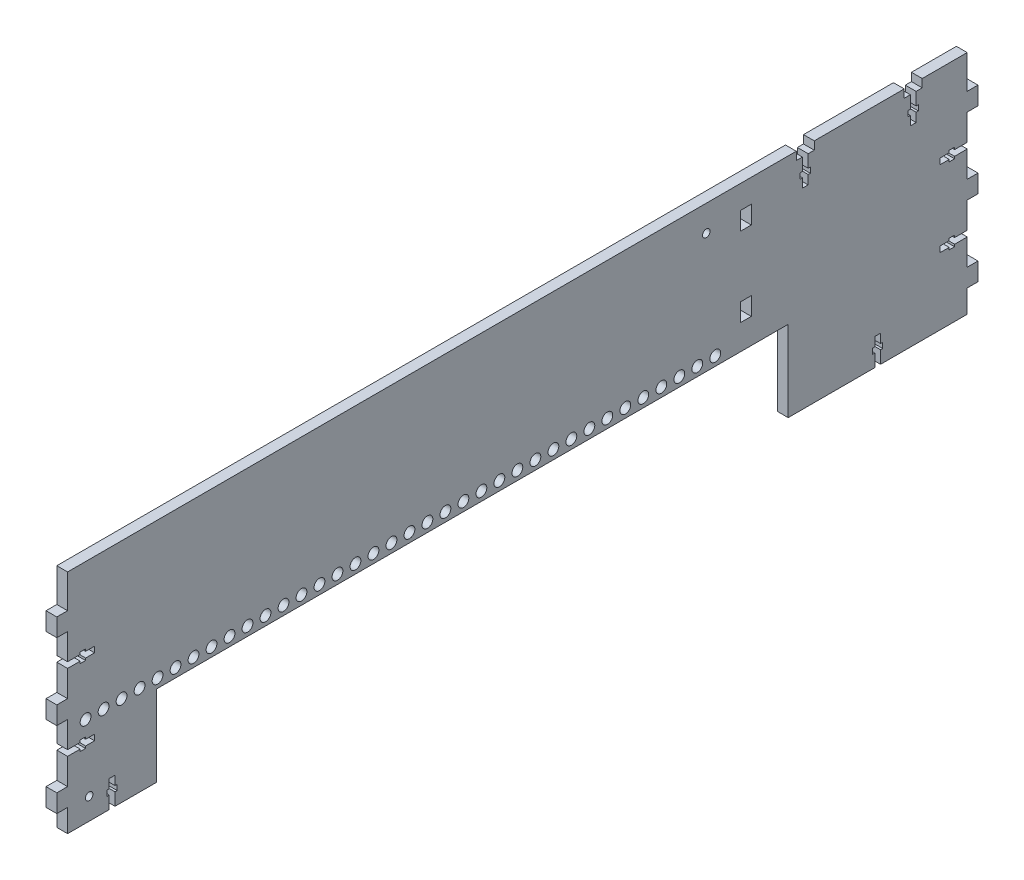
SolidWorks part; units mm, degrees
ref_plane "Front Plane" through (0, 0, 0) normal (0, 0, 1) x (1, 0, 0)
ref_plane "Top Plane" through (0, 0, 0) normal (0, 1, 0) x (1, 0, 0)
ref_plane "Right Plane" through (0, 0, 0) normal (1, 0, 0) x (0, 0, -1)
sketch "Sketch1" plane through (0, 0, 0) normal (1, 0, 0) x (0, 0, -1)
  line L1 (-250, -63) -> (250, -63)
  line L2 (-250, -63) -> (-250, 63)
  line L3 (-250, 63) -> (250, 63)
  line L4 (250, -63) -> (250, 63)
  line L5 (-250, -63) -> (250, 63) construction
  line L6 (-250, 63) -> (250, -63) construction
  point P0 (0, 0)
  dimension "D1" = 126
  dimension "D2" = 500
extrude "Boss-Extrude1" add sketch "Sketch1" along normal blind 6
sketch "Sketch4" plane through (0, 0, 250) normal (0, 0, 1) x (1, 0, 0)
  line L0 (0, 63) -> (0, -63) construction
  line L1 (0, 44.3321) -> (6, 44.3321)
  line L2 (0, 44.3321) -> (0, 34.3321)
  line L3 (0, 34.3321) -> (6, 34.3321)
  line L4 (6, 44.3321) -> (6, 34.3321)
  line L5 (6, 63) -> (6, -63) construction
  line L6 (0, 34.3321) -> (6, 34.3321) construction
  line L7 (0, -69) -> (0, 63) construction
  line L8 (6, 44.3321) -> (0, 44.3321) construction
  line L9 (0, -8) -> (6, -8) construction
  line L10 (0, -8) -> (6, -8)
  line L11 (0, -8) -> (0, 2)
  line L12 (0, 2) -> (6, 2)
  line L13 (6, -8) -> (6, 2)
  line L14 (6, -69) -> (6, 63) construction
  line L15 (6, 2) -> (0, 2) construction
  line L16 (6, -40.3321) -> (0, -40.3321) construction
  line L17 (0, -50.3321) -> (6, -50.3321)
  line L18 (0, -50.3321) -> (0, -40.3321)
  line L19 (0, -40.3321) -> (6, -40.3321)
  line L20 (6, -50.3321) -> (6, -40.3321)
  line L21 (0, -50.3321) -> (6, -50.3321) construction
extrude "Boss-Extrude2" add sketch "Sketch4" along normal blind 6
sketch "Sketch5" plane through (0, 0, 0) normal (-1, 0, 0) x (0, 0, 1)
  line L1 (250, 19.7661) -> (250, 16.5661) construction
  line L3 (250, 19.7661) -> (250, 16.5661) construction
  line L4 (250, -22.5661) -> (250, -25.7661) construction
  line L5 (250, -22.5661) -> (250, -25.7661) construction
  line L6 (250, 18.1661) -> (235, 18.1661) construction
  line L7 (250, -24.1661) -> (235, -24.1661) construction
  line L8 (250, -22.5661) -> (243, -22.5661)
  line L9 (250, 19.7661) -> (243, 19.7661)
  line L10 (250, -25.7661) -> (243, -25.7661)
  line L11 (250, 16.5661) -> (243, 16.5661)
  line L12 (250, -22.5661) -> (250, -25.7661)
  line L13 (235, -22.5661) -> (235, -25.7661)
  line L14 (250, 19.7661) -> (250, 16.5661)
  line L15 (235, 19.7661) -> (235, 16.5661)
  line L16 (240, 16.5661) -> (235, 16.5661)
  line L17 (243, 15.3661) -> (240, 15.3661)
  line L18 (243, 15.3661) -> (243, 16.5661)
  line L19 (243, 20.9661) -> (240, 20.9661)
  line L20 (240, 15.3661) -> (240, 16.5661)
  line L21 (243, 15.3661) -> (240, 20.9661) construction
  line L22 (243, 20.9661) -> (240, 15.3661) construction
  line L23 (243, -26.9661) -> (240, -26.9661)
  line L24 (243, -26.9661) -> (243, -25.7661)
  line L25 (243, -21.3661) -> (240, -21.3661)
  line L26 (240, -26.9661) -> (240, -25.7661)
  line L27 (243, -26.9661) -> (240, -21.3661) construction
  line L28 (243, -21.3661) -> (240, -26.9661) construction
  line L29 (250, 16.5661) -> (235, 16.5661) construction
  line L30 (243, 19.7661) -> (243, 20.9661)
  line L31 (240, 19.7661) -> (235, 19.7661)
  line L32 (250, 19.7661) -> (235, 19.7661) construction
  line L33 (240, 19.7661) -> (240, 20.9661)
  line L34 (240, -22.5661) -> (235, -22.5661)
  line L35 (250, -22.5661) -> (235, -22.5661) construction
  line L36 (240, -22.5661) -> (240, -21.3661)
  line L37 (240, -25.7661) -> (235, -25.7661)
  line L38 (250, -25.7661) -> (235, -25.7661) construction
  line L39 (243, -22.5661) -> (243, -21.3661)
  point P20 (241.5, 18.1661)
  point P25 (241.5, -24.1661)
  line M35 (250, -40.3321) -> (250, -8)
  line M39 (250, 2) -> (250, 34.3321)
  dimension "D3" = 1.6
  dimension "D4" = 7
  dimension "D5" = 3
  dimension "D6" = 5.6
  dimension "D1" = 15
  dimension "D7" = 7
  dimension "D8" = 3
  dimension "D9" = 5.6
  dimension "D2" = 1.6
extrude "Cut-Extrude3" cut sketch "Sketch5" against normal up to next contours L12 | L8 L39 L25 L36 L34 L13 L37 L26 L23 L24 L10 M35 | L33 L31 L15 L16 L20 L17 L18 L11 L9 L30 L19 M39 region at (0, -24.1661, 242.3696) region at (0, 18.1661, 242.3696)
sketch "Sketch6" plane through (0, 0, -250) normal (0, 0, -1) x (-1, 0, 0)
  line L0 (0, 44.3321) -> (0, 34.3321) construction
  line L1 (0, 34.3321) -> (-6, 34.3321) construction
  line L2 (-6, 34.3321) -> (-6, 44.3321) construction
  line L3 (-6, 44.3321) -> (0, 44.3321) construction
  line L4 (0, 2) -> (0, -8) construction
  line L5 (0, -8) -> (-6, -8) construction
  line L6 (-6, -8) -> (-6, 2) construction
  line L7 (-6, 2) -> (0, 2) construction
  line L8 (0, -40.3321) -> (0, -50.3321) construction
  line L9 (0, -50.3321) -> (-6, -50.3321) construction
  line L10 (-6, -50.3321) -> (-6, -40.3321) construction
  line L11 (-6, -40.3321) -> (0, -40.3321) construction
  line L12 (0, 44.3321) -> (0, 34.3321)
  line L13 (0, 34.3321) -> (-6, 34.3321)
  line L14 (-6, 34.3321) -> (-6, 44.3321)
  line L15 (-6, 44.3321) -> (0, 44.3321)
  line L16 (0, 2) -> (0, -8)
  line L17 (0, -8) -> (-6, -8)
  line L18 (-6, -8) -> (-6, 2)
  line L19 (-6, 2) -> (0, 2)
  line L20 (0, -40.3321) -> (0, -50.3321)
  line L21 (0, -50.3321) -> (-6, -50.3321)
  line L22 (-6, -50.3321) -> (-6, -40.3321)
  line L23 (-6, -40.3321) -> (0, -40.3321)
extrude "Boss-Extrude3" add sketch "Sketch6" along normal blind 6
sketch "Sketch7" plane through (0, 0, 0) normal (-1, 0, 0) x (0, 0, 1)
  line L0 (243, 16.5661) -> (250, 16.5661) construction
  line L2 (243, 16.5661) -> (243, 15.3661) construction
  line L3 (240, 15.3661) -> (243, 15.3661) construction
  line L4 (240, 16.5661) -> (240, 15.3661) construction
  line L5 (235, 16.5661) -> (240, 16.5661) construction
  line L6 (235, 16.5661) -> (235, 19.7661) construction
  line L7 (235, 19.7661) -> (240, 19.7661) construction
  line L8 (240, 20.9661) -> (240, 19.7661) construction
  line L9 (240, 20.9661) -> (243, 20.9661) construction
  line L10 (243, 20.9661) -> (243, 19.7661) construction
  line L11 (243, 19.7661) -> (250, 19.7661) construction
  line L12 (243, 16.5661) -> (250, 16.5661) construction
  line L13 (243, 16.5661) -> (243, 15.3661) construction
  line L14 (240, 15.3661) -> (243, 15.3661) construction
  line L15 (240, 16.5661) -> (240, 15.3661) construction
  line L16 (235, 16.5661) -> (240, 16.5661) construction
  line L17 (235, 16.5661) -> (235, 19.7661) construction
  line L18 (235, 19.7661) -> (240, 19.7661) construction
  line L19 (240, 20.9661) -> (240, 19.7661) construction
  line L20 (240, 20.9661) -> (243, 20.9661) construction
  line L21 (243, 20.9661) -> (243, 19.7661) construction
  line L22 (243, 19.7661) -> (250, 19.7661) construction
  line L23 (235, -25.7661) -> (240, -25.7661) construction
  line L24 (240, -25.7661) -> (240, -26.9661) construction
  line L25 (240, -26.9661) -> (243, -26.9661) construction
  line L26 (243, -25.7661) -> (243, -26.9661) construction
  line L27 (243, -25.7661) -> (250, -25.7661) construction
  line L28 (243, -22.5661) -> (250, -22.5661) construction
  line L29 (243, -21.3661) -> (243, -22.5661) construction
  line L30 (240, -21.3661) -> (243, -21.3661) construction
  line L31 (240, -21.3661) -> (240, -22.5661) construction
  line L32 (235, -22.5661) -> (240, -22.5661) construction
  line L33 (235, -25.7661) -> (235, -22.5661) construction
  line L34 (235, -25.7661) -> (240, -25.7661) construction
  line L35 (240, -25.7661) -> (240, -26.9661) construction
  line L36 (240, -26.9661) -> (243, -26.9661) construction
  line L37 (243, -25.7661) -> (243, -26.9661) construction
  line L38 (243, -25.7661) -> (250, -25.7661) construction
  line L39 (243, -22.5661) -> (250, -22.5661) construction
  line L40 (243, -21.3661) -> (243, -22.5661) construction
  line L41 (240, -21.3661) -> (243, -21.3661) construction
  line L42 (240, -21.3661) -> (240, -22.5661) construction
  line L43 (235, -22.5661) -> (240, -22.5661) construction
  line L44 (235, -25.7661) -> (235, -22.5661) construction
  line L45 (0, 0) -> (0, 57.5645) construction
  line L46 (-235, -25.7661) -> (-235, -22.5661)
  line L47 (-235, -22.5661) -> (-240, -22.5661)
  line L48 (-240, -21.3661) -> (-240, -22.5661)
  line L49 (-240, -21.3661) -> (-243, -21.3661)
  line L50 (-243, -21.3661) -> (-243, -22.5661)
  line L51 (-243, -22.5661) -> (-250, -22.5661)
  line L52 (-243, -25.7661) -> (-250, -25.7661)
  line L53 (-243, -25.7661) -> (-243, -26.9661)
  line L54 (-240, -26.9661) -> (-243, -26.9661)
  line L55 (-240, -25.7661) -> (-240, -26.9661)
  line L56 (-235, -25.7661) -> (-240, -25.7661)
  line L57 (-243, 19.7661) -> (-250, 19.7661)
  line L58 (-243, 20.9661) -> (-243, 19.7661)
  line L59 (-240, 20.9661) -> (-243, 20.9661)
  line L60 (-240, 20.9661) -> (-240, 19.7661)
  line L61 (-235, 19.7661) -> (-240, 19.7661)
  line L62 (-235, 16.5661) -> (-235, 19.7661)
  line L63 (-235, 16.5661) -> (-240, 16.5661)
  line L64 (-240, 16.5661) -> (-240, 15.3661)
  line L65 (-240, 15.3661) -> (-243, 15.3661)
  line L66 (-243, 16.5661) -> (-243, 15.3661)
  line L67 (-243, 16.5661) -> (-250, 16.5661)
  line L68 (-250, 19.7661) -> (-250, 16.5661)
  line L69 (-250, -22.5661) -> (-250, -25.7661)
extrude "Cut-Extrude4" cut sketch "Sketch7" against normal up to next
sketch "Sketch8" plane through (0, 0, 0) normal (-1, 0, 0) x (0, 0, 1)
  line L0 (200, -18.55) -> (-150, -18.55) construction
  line L1 (200, -18.55) -> (-150, -18.55) construction
  line L2 (200, -18.55) -> (200, -63) construction
  line L3 (200, -18.55) -> (200, -63) construction
  line L186 (-150, -18.55) -> (-150, -63) construction
  line L187 (-150, -63) -> (200, -63) construction
  line L188 (200.5, -18.05) -> (200.5, -63)
  line L189 (200.5, -18.05) -> (-150.5, -18.05)
  line L190 (-150.5, -18.05) -> (-150.5, -63)
  line L191 (-150.5, -63) -> (200.5, -63)
  dimension "D1" = 0.5
extrude "Cut-Extrude5" cut sketch "Sketch8" against normal up to next
sketch "Sketch11" plane through (6, 0, 0) normal (1, 0, 0) x (0, 0, -1)
  line L0 (130, 40) -> (130, 50) construction
  line L1 (130, 50) -> (124, 50) construction
  line L2 (124, 50) -> (124, 40) construction
  line L3 (124, 40) -> (130, 40) construction
  line L4 (130, -4) -> (130, 6) construction
  line L5 (130, 6) -> (124, 6) construction
  line L6 (124, 6) -> (124, -4) construction
  line L7 (124, -4) -> (130, -4) construction
  line L8 (130, 40) -> (130, 50)
  line L9 (130, 50) -> (124, 50)
  line L10 (124, 50) -> (124, 40)
  line L11 (124, 40) -> (130, 40)
  line L12 (130, -4) -> (130, 6)
  line L13 (130, 6) -> (124, 6)
  line L14 (124, 6) -> (124, -4)
  line L15 (124, -4) -> (130, -4)
extrude "Cut-Extrude8" cut sketch "Sketch11" against normal up to next
sketch "Sketch12" plane through (0, 0, 0) normal (-1, 0, 0) x (0, 0, 1)
  line L0 (-124, 50) -> (-124, 40) construction
  line L1 (-250, 63) -> (250, 63) construction
  circle A0 centre (-105, 48.5) radius 2.1
  dimension "D1" = 19
  dimension "D3" = 4.2
  dimension "D2" = 14.5
extrude "Cut-Extrude9" cut sketch "Sketch12" against normal up to next
sketch "Sketch13" plane through (0, 63, 0) normal (0, 1, 0) x (1, 0, 0)
  line L0 (6, 250) -> (6, -250) construction
  line L1 (0, 215) -> (6, 215)
  line L2 (0, 215) -> (0, 225)
  line L3 (0, 225) -> (6, 225)
  line L4 (6, 215) -> (6, 225)
  line L5 (0, 215) -> (6, 225) construction
  line L6 (0, 225) -> (6, 215) construction
  line L7 (6, 225) -> (0, 225) construction
  line L8 (6, 165) -> (0, 165) construction
  line L9 (0, 155) -> (6, 155)
  line L10 (0, 155) -> (0, 165)
  line L11 (0, 165) -> (6, 165)
  line L12 (6, 155) -> (6, 165)
  line L13 (0, 155) -> (6, 165) construction
  line L14 (0, 165) -> (6, 155) construction
  point P0 (3, 220)
  point P10 (3, 160)
extrude "Cut-Extrude10" cut sketch "Sketch13" against normal blind 4.5
sketch "Sketch14" plane through (0, 0, 0) normal (-1, 0, 0) x (0, 0, 1)
  circle A0 centre (240, -13) radius 3 construction
  circle A1 centre (240, -13) radius 3
  circle A2 centre (230, -13) radius 3
  circle A3 centre (220, -13) radius 3
  circle A4 centre (210, -13) radius 3
  circle A5 centre (200, -13) radius 3
  circle A6 centre (190, -13) radius 3
  circle A7 centre (180, -13) radius 3
  circle A8 centre (170, -13) radius 3
  circle A9 centre (160, -13) radius 3
  circle A10 centre (150, -13) radius 3
  circle A11 centre (140, -13) radius 3
  circle A12 centre (130, -13) radius 3
  circle A13 centre (120, -13) radius 3
  circle A14 centre (110, -13) radius 3
  circle A15 centre (100, -13) radius 3
  circle A16 centre (90, -13) radius 3
  circle A17 centre (80, -13) radius 3
  circle A18 centre (70, -13) radius 3
  circle A19 centre (60, -13) radius 3
  circle A20 centre (50, -13) radius 3
  circle A21 centre (40, -13) radius 3
  circle A22 centre (30, -13) radius 3
  circle A23 centre (20, -13) radius 3
  circle A24 centre (10, -13) radius 3
  circle A25 centre (0, -13) radius 3
  circle A26 centre (-10, -13) radius 3
  circle A27 centre (-20, -13) radius 3
  circle A28 centre (-30, -13) radius 3
  circle A29 centre (-40, -13) radius 3
  circle A30 centre (-50, -13) radius 3
  circle A31 centre (-60, -13) radius 3
  circle A32 centre (-70, -13) radius 3
  circle A33 centre (-80, -13) radius 3
  circle A34 centre (-90, -13) radius 3
  circle A35 centre (-100, -13) radius 3
  circle A36 centre (-110, -13) radius 3
  dimension "D1" = 36
extrude "Cut-Extrude11" cut sketch "Sketch14" against normal up to next (6 mm away)
sketch "Sketch15" plane through (6, 0, 0) normal (1, 0, 0) x (0, 0, -1)
  line L0 (160, 58.5) -> (160, 43.5) construction
  line L1 (155, 58.5) -> (165, 58.5) construction
  line L2 (220, 58.5) -> (220, 43.5) construction
  line L3 (215, 58.5) -> (225, 58.5) construction
  line L4 (160, 43.5) -> (220, 43.5) construction
  line L5 (190, 43.5) -> (190, 63) construction
  line L6 (215, 63) -> (165, 63) construction
  line L7 (158.4, 58.5) -> (158.4, 51.5)
  line L8 (161.6, 58.5) -> (161.6, 51.5)
  line L9 (158.4, 58.5) -> (161.6, 58.5)
  line L10 (158.4, 43.5) -> (161.6, 43.5)
  line L11 (161.6, 48.5) -> (162.8, 48.5)
  line L12 (157.2, 51.5) -> (158.4, 51.5)
  line L13 (157.2, 51.5) -> (157.2, 48.5)
  line L14 (157.2, 48.5) -> (158.4, 48.5)
  line L15 (162.8, 51.5) -> (162.8, 48.5)
  line L16 (157.2, 51.5) -> (162.8, 48.5) construction
  line L17 (157.2, 48.5) -> (162.8, 51.5) construction
  line L18 (161.6, 51.5) -> (162.8, 51.5)
  line L19 (158.4, 48.5) -> (158.4, 43.5)
  line L20 (158.4, 58.5) -> (158.4, 43.5) construction
  line L21 (161.6, 48.5) -> (161.6, 43.5)
  line L22 (161.6, 58.5) -> (161.6, 43.5) construction
  line L23 (222.8, 48.5) -> (217.2, 51.5) construction
  line L24 (222.8, 51.5) -> (217.2, 48.5) construction
  line L25 (220, 58.5) -> (220, 43.5) construction
  line L26 (218.4, 48.5) -> (218.4, 43.5)
  line L27 (221.6, 48.5) -> (221.6, 43.5)
  line L28 (218.4, 51.5) -> (217.2, 51.5)
  line L29 (217.2, 51.5) -> (217.2, 48.5)
  line L30 (222.8, 48.5) -> (221.6, 48.5)
  line L31 (222.8, 51.5) -> (222.8, 48.5)
  line L32 (222.8, 51.5) -> (221.6, 51.5)
  line L33 (218.4, 48.5) -> (217.2, 48.5)
  line L34 (221.6, 43.5) -> (218.4, 43.5)
  line L35 (221.6, 58.5) -> (218.4, 58.5)
  line L36 (218.4, 58.5) -> (218.4, 51.5)
  line L37 (221.6, 58.5) -> (221.6, 51.5)
  point P16 (160, 50)
  point P37 (220, 50)
  dimension "D3" = 15
  dimension "D4" = 7
  dimension "D5" = 3
  dimension "D6" = 5.6
  dimension "D1" = 1.6
  dimension "D2" = 1.6
extrude "Cut-Extrude12" cut sketch "Sketch15" against normal up to next
sketch "Sketch16" plane through (6, 0, 0) normal (1, 0, 0) x (0, 0, -1)
  line L0 (-250, -63) -> (-200.5, -63) construction
  line L1 (-250, -63) -> (-200.5, -63) construction
  line L2 (-225.25, -63) -> (-225.25, -48) construction
  line L3 (-223.65, -63) -> (-223.65, -56)
  line L4 (-226.85, -63) -> (-226.85, -56)
  line L5 (-223.65, -63) -> (-226.85, -63)
  line L6 (-223.65, -48) -> (-226.85, -48)
  line L7 (-223.65, -53) -> (-223.65, -48)
  line L8 (-228.05, -56) -> (-226.85, -56)
  line L9 (-228.05, -56) -> (-228.05, -53)
  line L10 (-228.05, -53) -> (-226.85, -53)
  line L11 (-222.45, -56) -> (-222.45, -53)
  line L12 (-228.05, -56) -> (-222.45, -53) construction
  line L13 (-228.05, -53) -> (-222.45, -56) construction
  line L14 (-223.65, -63) -> (-223.65, -48) construction
  line L15 (-223.65, -53) -> (-222.45, -53)
  line L16 (-226.85, -53) -> (-226.85, -48)
  line L17 (-226.85, -63) -> (-226.85, -48) construction
  line L18 (-223.65, -56) -> (-222.45, -56)
  line L19 (150.5, -63) -> (250, -63) construction
  line L20 (150.5, -63) -> (250, -63) construction
  line L21 (200.25, -63) -> (200.25, -48) construction
  line L22 (201.85, -63) -> (201.85, -56)
  line L23 (198.65, -63) -> (198.65, -56)
  line L24 (201.85, -63) -> (198.65, -63)
  line L25 (201.85, -48) -> (198.65, -48)
  line L26 (201.85, -56) -> (203.05, -56)
  line L27 (197.45, -56) -> (198.65, -56)
  line L28 (197.45, -56) -> (197.45, -53)
  line L29 (197.45, -53) -> (198.65, -53)
  line L30 (203.05, -56) -> (203.05, -53)
  line L31 (197.45, -56) -> (203.05, -53) construction
  line L32 (197.45, -53) -> (203.05, -56) construction
  line L33 (201.85, -53) -> (201.85, -48)
  line L34 (201.85, -63) -> (201.85, -48) construction
  line L35 (201.85, -53) -> (203.05, -53)
  line L36 (198.65, -53) -> (198.65, -48)
  line L37 (198.65, -63) -> (198.65, -48) construction
  point P8 (-225.25, -54.5)
  point P25 (200.25, -54.5)
  dimension "D1" = 15
  dimension "D4" = 7
  dimension "D5" = 3
  dimension "D6" = 5.6
  dimension "D2" = 1.6
  dimension "D3" = 1.6
  dimension "D7" = 1.6
  dimension "D8" = 1.6
extrude "Cut-Extrude13" cut sketch "Sketch16" against normal through all
sketch "Sketch17" plane through (6, 0, 0) normal (1, 0, 0) x (0, 0, -1)
  circle A0 centre (-238, -51) radius 2.1 construction
  circle A1 centre (-238, -51) radius 2.1
extrude "Cut-Extrude14" cut sketch "Sketch17" against normal through all
